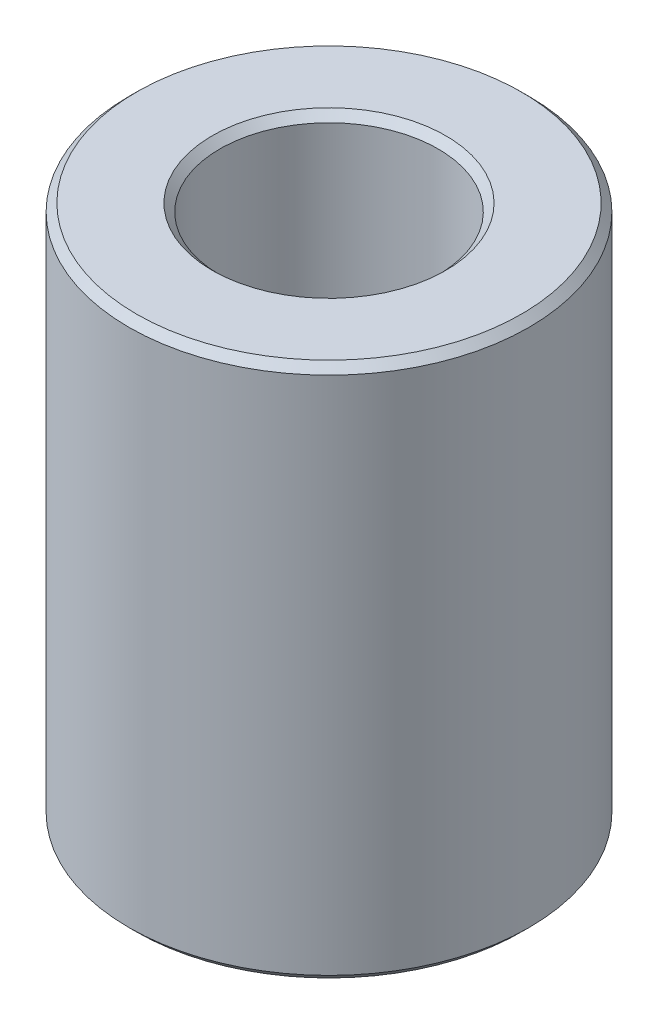
SolidWorks part; units mm, degrees
ref_plane "Front Plane" through (0, 0, 0) normal (0, 0, 1) x (1, 0, 0)
ref_plane "Top Plane" through (0, 0, 0) normal (0, 1, 0) x (1, 0, 0)
ref_plane "Right Plane" through (0, 0, 0) normal (1, 0, 0) x (0, 0, -1)
sketch "Sketch1" plane through (0, 0, 0) normal (0, 1, 0) x (1, 0, 0)
  circle A0 centre (0, 0) radius 15
  dimension "SLEEVE_OD" = 30
extrude "Boss-Extrude1" add sketch "Sketch1" along normal blind 40.1195
sketch "Sketch2" plane through (0, 0, 0) normal (0, 1, 0) x (1, 0, 0)
  circle A0 centre (0, 0) radius 8.1828
  dimension "BORE_D" = 16.3657
extrude "Cut-Extrude1" cut sketch "Sketch2" along normal through all
chamfer "Chamfer1" distance 0.5707 angle 45 4 edges at (0, 40.1195, 8.1828) (0, 0, 8.1828) (0, 0, 15) (0, 40.1195, 15)
